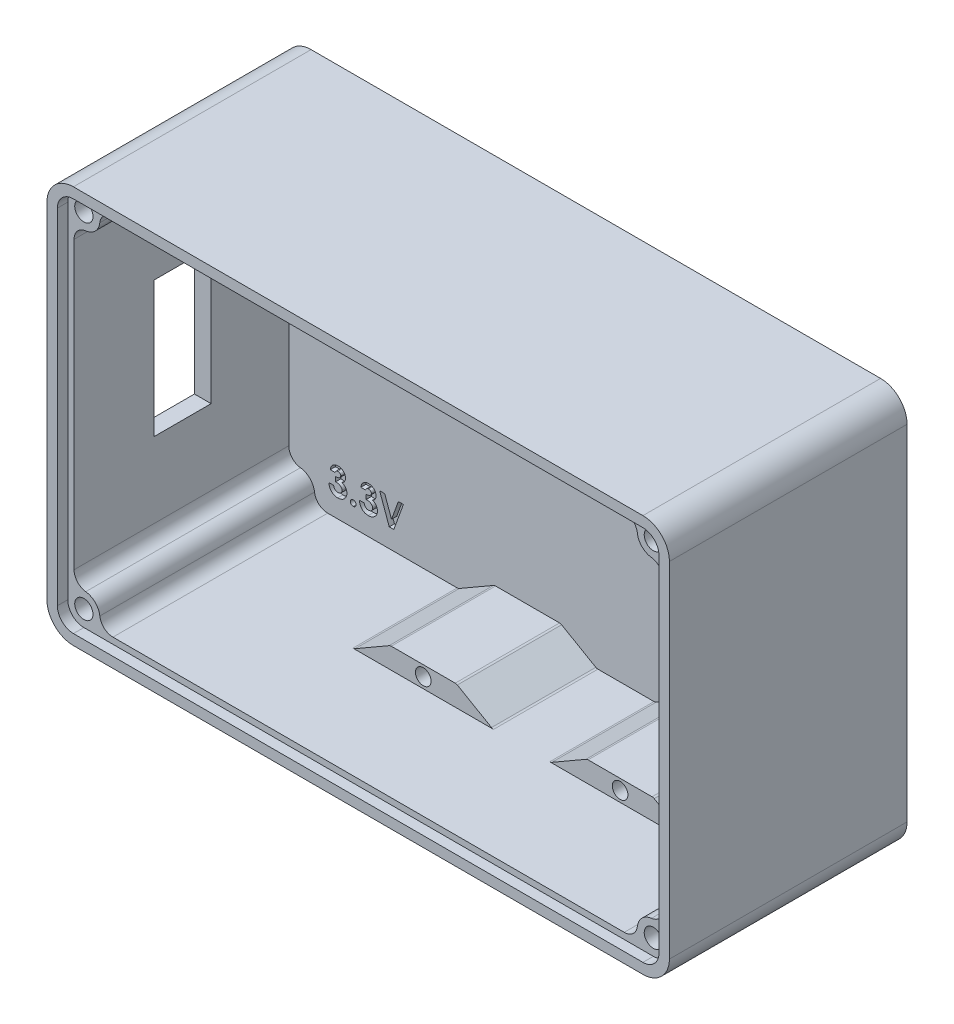
SolidWorks part; units mm, degrees
material "ABS"
ref_plane "Front Plane" through (0, 0, 0) normal (0, 0, 1) x (1, 0, 0)
ref_plane "Top Plane" through (0, 0, 0) normal (0, 1, 0) x (1, 0, 0)
ref_plane "Right Plane" through (0, 0, 0) normal (1, 0, 0) x (0, 0, -1)
sketch "OdroidOutline" plane through (0, 0, 0) normal (0, 0, 1) x (1, 0, 0)
  line L1 (42.5, -28) -> (-42.5, -28)
  line L2 (42.5, -28) -> (42.5, 28)
  line L3 (42.5, 28) -> (-42.5, 28)
  line L4 (-42.5, -28) -> (-42.5, 28)
  line L5 (42.5, -28) -> (-42.5, 28) construction
  line L6 (42.5, 28) -> (-42.5, -28) construction
  line L7 (-19, 24.5) -> (39, 24.5) construction
  line L8 (-19, 24.5) -> (-19, -24.5) construction
  line L9 (-19, -24.5) -> (39, -24.5) construction
  line L10 (39, 24.5) -> (39, -24.5) construction
  line L11 (-44, 25.54) -> (-22.3, 25.54)
  line L12 (-44, 25.54) -> (-44, 9.96)
  line L13 (-44, 9.96) -> (-22.3, 9.96)
  line L14 (-22.3, 25.54) -> (-22.3, 9.96)
  line L15 (-44, 5.565) -> (-26.44, 5.565)
  line L16 (-44, 5.565) -> (-44, -7.565)
  line L17 (-44, -7.565) -> (-26.44, -7.565)
  line L18 (-26.44, 5.565) -> (-26.44, -7.565)
  line L19 (-44, -12.435) -> (-26.44, -12.435)
  line L20 (-44, -12.435) -> (-44, -25.565)
  line L21 (-44, -25.565) -> (-26.44, -25.565)
  line L22 (-26.44, -12.435) -> (-26.44, -25.565)
  circle A0 centre (-19, 24.5) radius 1.25
  circle A1 centre (39, 24.5) radius 1.25
  circle A2 centre (39, -24.5) radius 1.25
  circle A3 centre (-19, -24.5) radius 1.25
  point P0 (0, 0)
  point P26 (-44, 17.75)
  point P27 (-44, -1)
  point P28 (-44, -19)
  dimension "D7" = 2.5
  dimension "D1" = 85
  dimension "D2" = 56
  dimension "D3" = 58
  dimension "D4" = 49
  dimension "D5" = 3.5
  dimension "D6" = 3.5
  dimension "D8" = 10.25
  dimension "D9" = 29
  dimension "D10" = 47
  dimension "D11" = 15.58
  dimension "D12" = 21.7
  dimension "D13" = 13.13
  dimension "D14" = 17.56
  dimension "D15" = 1.5
sketch "BatteryOutline" plane through (0, 0, 0) normal (0, 0, 1) x (1, 0, 0)
  line L0 (-3.8213, -21.195) -> (-3.8213, 21.195) construction
  line L2 (42.5, 0) -> (-3.8213, 0) construction
  line L3 (42.5, -28) -> (42.5, 28) construction
  line L4 (-3.8213, 21.195) -> (-3.8213, 24.5) construction
  line L7 (33.9287, -30.5) -> (-41.5713, -30.5)
  line L8 (33.9287, -30.5) -> (33.9287, 30.5)
  line L9 (33.9287, 30.5) -> (-41.5713, 30.5)
  line L10 (-41.5713, -30.5) -> (-41.5713, 30.5)
  line L11 (33.9287, -30.5) -> (-41.5713, 30.5) construction
  line L12 (33.9287, 30.5) -> (-41.5713, -30.5) construction
  circle A0 centre (-3.8213, 21.195) radius 1.75
  circle A1 centre (-3.8213, -21.195) radius 1.75
  point P3 (-3.8213, 0)
  dimension "D2" = 3.5
  dimension "D1" = 42.39
  dimension "D3" = 75.5
  dimension "D4" = 61
sketch "Sketch4" plane through (0, 0, 0) normal (0, 0, 1) x (1, 0, 0)
  line L0 (53.5, 0) -> (-53.5, 0) construction
  line L1 (53.5, -15) -> (53.5, 15) construction
  line L2 (-53.5, -15) -> (-53.5, 15) construction
  circle A0 centre (53.5, 15) radius 1.75
  circle A1 centre (-53.5, 15) radius 1.75
  circle A2 centre (-53.5, -15) radius 1.75
  circle A3 centre (53.5, -15) radius 1.75
  point P5 (0, 0)
  point P6 (53.5, 0)
  point P9 (-53.5, 0)
  dimension "D1" = 3.5
  dimension "D2" = 30
  dimension "D3" = 107
sketch "Sketch5" plane through (0, 0, 0) normal (0, 0, 1) x (1, 0, 0)
  line L0 (42.61, 34.9) -> (-66.61, 34.9)
  line L1 (42.61, -38.1) -> (-66.61, -38.1)
  line L2 (47.69, -33.02) -> (47.69, 33.02)
  line L3 (42.61, 38.1) -> (-66.61, 38.1)
  line L4 (-71.69, -33.02) -> (-71.69, 33.02)
  line L5 (47.69, -38.1) -> (-71.69, 38.1) construction
  line L6 (47.69, 38.1) -> (-71.69, -38.1) construction
  line L7 (-68.49, -33.02) -> (-68.49, 33.02)
  line L8 (42.61, -34.9) -> (-66.61, -34.9)
  line L9 (44.49, -33.02) -> (44.49, 33.02)
  line L10 (47.575, 0) -> (-47.575, 0) construction
  line L11 (0, 0) -> (0, 14.5835) construction
  arc A0 (-66.61, -38.1) -> (-71.69, -33.02) centre (-66.61, -33.02) cw
  arc A1 (42.61, -38.1) -> (47.69, -33.02) centre (42.61, -33.02) ccw
  arc A2 (47.69, 33.02) -> (42.61, 38.1) centre (42.61, 33.02) ccw
  arc A3 (-66.61, 38.1) -> (-71.69, 33.02) centre (-66.61, 33.02) ccw
  arc A4 (-66.61, 34.9) -> (-68.49, 33.02) centre (-66.61, 33.02) ccw
  arc A5 (-66.61, -34.9) -> (-68.49, -33.02) centre (-66.61, -33.02) cw
  arc A6 (42.61, -34.9) -> (44.49, -33.02) centre (42.61, -33.02) ccw
  arc A7 (44.49, 33.02) -> (42.61, 34.9) centre (42.61, 33.02) ccw
  point P16 (-12, 0)
  dimension "D6" = 5.08
  dimension "D2" = 119.38
  dimension "D4" = 12
  dimension "D3" = 3.2
extrude "Enclosure Base" add sketch "Sketch5" along normal blind 2.4 contours L3 A3 L4 A0 L1 A1 L2 A2
extrude "Enclosure Wall" add sketch "Sketch5<3>" along normal blind 43.18 from surface contours L3 A3 L4 A0 L1 A1 L2 A2 A7 L9 A6 L8 A5 L7 A4 L0 region at (-12, -36.6837, 0) starting at face at (-12, 0, 2.4)
sketch "Sketch5<3>" plane through (0, 0, 0) normal (0, 0, 1) x (1, 0, 0) same geometry as "Sketch5"
sketch "Sketch6" plane through (0, 0, 2.4) normal (0, 0, 1) x (1, 0, 0)
  line L0 (42.5, 28) -> (-42.5, 28) construction
  circle A0 centre (-19, 24.5) radius 3.5
  circle A1 centre (-19, -24.5) radius 3.5
  circle A2 centre (39, 24.5) radius 3.5
  circle A3 centre (39, -24.5) radius 3.5
  circle A4 centre (39, -24.5) radius 1.25 construction
  circle A5 centre (39, 24.5) radius 1.25 construction
  circle A6 centre (-19, -24.5) radius 1.25 construction
  circle A7 centre (-19, 24.5) radius 1.25 construction
  circle A8 centre (39, -24.5) radius 1.25
  circle A9 centre (39, 24.5) radius 1.25
  circle A10 centre (-19, -24.5) radius 1.25
  circle A11 centre (-19, 24.5) radius 1.25
extrude "Odroid Mount Spacer" [suppressed] add sketch "Sketch6" along normal blind 15
sketch "Sketch7" plane through (-71.69, 0, 0) normal (-1, 0, 0) x (0, 0, 1)
  line L0 (47.575, 0) -> (-47.575, 0) construction
  line L1 (28.29, -13) -> (17.29, -13)
  line L2 (28.29, -13) -> (28.29, 13)
  line L3 (28.29, 13) -> (17.29, 13)
  line L4 (17.29, -13) -> (17.29, 13)
  line L5 (28.29, -13) -> (17.29, 13) construction
  line L6 (28.29, 13) -> (17.29, -13) construction
  line L7 (22.79, 33.02) -> (22.79, 0) construction
  line L8 (45.58, 33.02) -> (0, 33.02) construction
  point P0 (22.79, 0)
  dimension "D1" = 26
  dimension "D2" = 11
extrude "Power Switch Hole" cut sketch "Sketch7" against normal blind 7.112
sketch "Sketch8" plane through (0, 0, 2.4) normal (0, 0, 1) x (1, 0, 0)
  line L0 (-60.9934, 25.8776) -> (-60.9934, -31.2724) construction
  line L4 (47.69, 38.1) -> (-71.69, -38.1) construction
  text T0 "<b>3.3V</b>" font "Century Gothic" height 5.08
  text T1 "<b>5.0V</b>" font "Century Gothic" height 5.08
  text T2 "<b>Vin</b>" font "Century Gothic" height 3.175
  dimension "D1" = 57.15
extrude "Labeling" cut sketch "Sketch8" against normal blind 1
sketch "Sketch9" plane through (0, 0, 45.58) normal (0, 0, 1) x (1, 0, 0)
  line L0 (42.61, 34.9) -> (-66.61, 34.9) construction
  line L1 (44.49, -33.02) -> (44.49, 33.02) construction
  line L2 (42.61, -34.9) -> (-66.61, -34.9) construction
  line L3 (-68.49, -33.02) -> (-68.49, 33.02) construction
  line L4 (44.49, -33.02) -> (44.49, 33.02)
  line L5 (42.61, -34.9) -> (-66.61, -34.9)
  line L6 (-68.49, -33.02) -> (-68.49, 33.02)
  line L7 (42.61, 34.9) -> (-66.61, 34.9)
  line L8 (42.61, 36.1) -> (-66.61, 36.1)
  line L9 (-69.69, 33.02) -> (-69.69, -33.02)
  line L10 (-66.61, -36.1) -> (42.61, -36.1)
  line L11 (45.69, -33.02) -> (45.69, 33.02)
  line L12 (42.61, 36.1) -> (-66.61, 36.1)
  line L13 (-69.69, 33.02) -> (-69.69, -33.02)
  line L14 (-66.61, -36.1) -> (42.61, -36.1)
  line L15 (45.69, -33.02) -> (45.69, 33.02)
  arc A0 (44.49, 33.02) -> (42.61, 34.9) centre (42.61, 33.02) ccw construction
  arc A1 (42.61, -34.9) -> (44.49, -33.02) centre (42.61, -33.02) ccw construction
  arc A2 (-68.49, -33.02) -> (-66.61, -34.9) centre (-66.61, -33.02) ccw construction
  arc A3 (-66.61, 34.9) -> (-68.49, 33.02) centre (-66.61, 33.02) ccw construction
  arc A4 (44.49, 33.02) -> (42.61, 34.9) centre (42.61, 33.02) ccw
  arc A5 (42.61, -34.9) -> (44.49, -33.02) centre (42.61, -33.02) ccw
  arc A6 (-68.49, -33.02) -> (-66.61, -34.9) centre (-66.61, -33.02) ccw
  arc A7 (-66.61, 34.9) -> (-68.49, 33.02) centre (-66.61, 33.02) ccw
  arc A8 (45.69, 33.02) -> (42.61, 36.1) centre (42.61, 33.02) ccw
  arc A9 (-66.61, 36.1) -> (-69.69, 33.02) centre (-66.61, 33.02) ccw
  arc A10 (-69.69, -33.02) -> (-66.61, -36.1) centre (-66.61, -33.02) ccw
  arc A11 (42.61, -36.1) -> (45.69, -33.02) centre (42.61, -33.02) ccw
  arc A12 (45.69, 33.02) -> (42.61, 36.1) centre (42.61, 33.02) ccw
  arc A13 (-66.61, 36.1) -> (-69.69, 33.02) centre (-66.61, 33.02) ccw
  arc A14 (-69.69, -33.02) -> (-66.61, -36.1) centre (-66.61, -33.02) ccw
  arc A15 (42.61, -36.1) -> (45.69, -33.02) centre (42.61, -33.02) ccw
extrude "Top Cover Groove" cut sketch "Sketch9" against normal blind 2
sketch "Sketch10" plane through (0, 0, 0) normal (0, 0, 1) x (1, 0, 0)
  circle A0 centre (-66.61, 33.02) radius 3.08
  circle A1 centre (-66.61, -33.02) radius 3.08
  circle A2 centre (42.61, 33.02) radius 3.08
  circle A3 centre (42.61, -33.02) radius 3.08
  arc A4 (45.69, 33.02) -> (42.61, 36.1) centre (42.61, 33.02) ccw construction
  arc A5 (-66.61, 36.1) -> (-69.69, 33.02) centre (-66.61, 33.02) ccw construction
  arc A6 (-69.69, -33.02) -> (-66.61, -36.1) centre (-66.61, -33.02) ccw construction
  arc A7 (42.61, -36.1) -> (45.69, -33.02) centre (42.61, -33.02) ccw construction
  circle A8 centre (-66.61, 33.02) radius 1.75
  circle A9 centre (-66.61, -33.02) radius 1.75
  circle A10 centre (42.61, -33.02) radius 1.75
  circle A11 centre (42.61, 33.02) radius 1.75
  dimension "D1" = 3.5
extrude "Boss-Extrude4" add sketch "Sketch10" along normal up to surface (43.58 mm away) up to face at (-12, 0, 43.58)
fillet "Fillet1" radius 2.54 8 edges at (44.49, 30.5803, 22.99) (40.1703, 34.9, 22.99) (-64.1703, 34.9, 22.99) (-68.49, 30.5803, 22.99) (-68.49, -30.5803, 22.99) (-64.1703, -34.9, 22.99) (40.1703, -34.9, 22.99) (44.49, -30.5803, 22.99)
sketch "Sketch11" plane through (0, 0, 2.4) normal (0, 0, 1) x (1, 0, 0)
  line L1 (-29.649, 7.2199) -> (-52.199, 7.2199)
  line L2 (-29.649, 7.2199) -> (-29.649, 24.5199)
  line L3 (-29.649, 24.5199) -> (-52.199, 24.5199)
  line L4 (-52.199, 7.2199) -> (-52.199, 24.5199)
  line L5 (-29.649, 7.2199) -> (-52.199, 24.5199) construction
  line L6 (-29.649, 24.5199) -> (-52.199, 7.2199) construction
  point P0 (-40.924, 15.8699)
  dimension "D1" = 17.3
  dimension "D2" = 22.55
sketch "Sketch12" plane through (0, 0, 2.4) normal (0, 0, 1) x (1, 0, 0)
  line L0 (-22.6963, 30.5) -> (-22.6963, 30.9) construction
  line L1 (-9.4181, 34.9) -> (-35.9745, 34.9)
  line L2 (-9.4181, 34.9) -> (-16.3463, 30.9)
  line L3 (42.61, 34.9) -> (-66.61, 34.9) construction
  line L4 (-3.8213, 30.5) -> (-3.8213, 34.9) construction
  line L5 (-61.0289, 34.9) -> (37.0289, 34.9) construction
  line L6 (8.7037, 30.9) -> (21.4037, 30.9)
  line L7 (28.3319, 34.9) -> (21.4037, 30.9)
  line L8 (1.7755, 34.9) -> (28.3319, 34.9)
  line L9 (1.7755, 34.9) -> (8.7037, 30.9)
  line L10 (-41.5713, 30.5) -> (-3.8213, 30.5) construction
  line L11 (-41.5713, -30.5) -> (-41.5713, 30.5) construction
  line L12 (-16.3463, 30.9) -> (-29.0463, 30.9)
  line L13 (-35.9745, 34.9) -> (-29.0463, 30.9)
  line L14 (-9.4181, 34.9) -> (-29.0463, 30.9) construction
  line L15 (-16.3463, 30.9) -> (-35.9745, 34.9) construction
  line L16 (33.9287, 30.5) -> (-41.5713, 30.5) construction
  line L17 (37.0289, 34.9) -> (-61.0289, 34.9) construction
  line L18 (-3.8213, -30.5) -> (-3.8213, -34.9) construction
  line L19 (33.9287, -30.5) -> (-41.5713, -30.5) construction
  line L20 (-61.0289, -34.9) -> (37.0289, -34.9) construction
  line L21 (-41.5713, -30.5) -> (-3.8213, -30.5) construction
  line L22 (-35.1963, -30.9) -> (-10.1963, -30.9) construction
  line L23 (-10.1963, -30.9) -> (-10.1963, -32.9) construction
  line L24 (-10.1963, -32.9) -> (-18.6963, -32.9) construction
  line L25 (-18.6963, -32.9) -> (-18.6963, -34.9) construction
  line L26 (-18.6963, -34.9) -> (-26.6963, -34.9) construction
  line L27 (-26.6963, -34.9) -> (-26.6963, -32.9) construction
  line L28 (-26.6963, -32.9) -> (-35.1963, -32.9) construction
  line L29 (-35.1963, -32.9) -> (-35.1963, -30.9) construction
  line L30 (-22.6963, -30.5) -> (-22.6963, -34.9) construction
  line L31 (19.0537, -32.9) -> (27.5537, -32.9) construction
  line L32 (19.0537, -34.9) -> (19.0537, -32.9) construction
  line L33 (11.0537, -34.9) -> (19.0537, -34.9) construction
  line L34 (11.0537, -32.9) -> (11.0537, -34.9) construction
  line L35 (2.5537, -32.9) -> (11.0537, -32.9) construction
  line L36 (2.5537, -30.9) -> (2.5537, -32.9) construction
  line L37 (27.5537, -30.9) -> (2.5537, -30.9) construction
  line L38 (27.5537, -32.9) -> (27.5537, -30.9) construction
  line L43 (33.9287, -30.5) -> (33.9287, 30.5) construction
  line L44 (34.3287, 25.25) -> (40.3287, 19.25)
  line L45 (34.3287, 25.25) -> (34.3287, 5.25)
  line L46 (34.3287, 5.25) -> (40.3287, 11.25)
  line L47 (40.3287, 19.25) -> (40.3287, 11.25) construction
  line L48 (33.9287, 0) -> (44.49, 0) construction
  line L49 (44.49, 27.4389) -> (44.49, -27.4389) construction
  line L50 (33.9287, 0) -> (33.9287, 30.5) construction
  line L51 (33.9287, 15.25) -> (34.3287, 15.25) construction
  line L56 (-22.6963, 30.9) -> (-22.6963, 34.8972) construction
  line L57 (25.069, 0) -> (-25.069, 0) construction
  line L58 (40.3287, 19.25) -> (44.49, 19.25)
  line L59 (44.49, -27.4389) -> (44.49, 27.4389) construction
  line L60 (44.49, 19.25) -> (44.49, 11.25)
  line L61 (44.49, 11.25) -> (40.3287, 11.25)
  line L62 (44.49, -19.25) -> (44.49, -11.25)
  line L63 (40.3287, -19.25) -> (44.49, -19.25)
  line L64 (34.3287, -25.25) -> (40.3287, -19.25)
  line L65 (34.3287, -25.25) -> (34.3287, -5.25)
  line L66 (34.3287, -5.25) -> (40.3287, -11.25)
  line L67 (44.49, -11.25) -> (40.3287, -11.25)
  circle A0 centre (-22.6963, 32.8986) radius 1.5
  circle A1 centre (15.0537, 32.8986) radius 1.5
  circle A2 centre (-22.6963, -32.8986) radius 1.5
  circle A3 centre (15.0537, -32.8986) radius 1.5
  point P0 (-22.6963, 32.1941)
  point P22 (-8.875, 30.5)
  point P24 (-22.6963, 30.5)
  point P30 (-22.6963, -30.5)
  point P46 (-22.6963, -30.9)
  point P68 (33.9287, 15.25)
  dimension "D13" = 3
  dimension "D1" = 0.4
  dimension "D2" = 30
  dimension "D3" = 30
  dimension "D4" = 2
  dimension "D5" = 0.4
  dimension "D6" = 8
  dimension "D7" = 25
  dimension "D8" = 45
  dimension "D9" = 45
  dimension "D10" = 0.4
  dimension "D11" = 6
  dimension "D12" = 20
  dimension "D14" = 12.7
extrude "Boss-Extrude5" add sketch "Sketch12" along normal blind 20 contours L13 L1 L2 L12 A0 | L9 L8 L7 L6 A1 region at (-13.0165, 33.1326, 2.4) region at (5.3739, 33.1326, 2.4)
extrude "Boss-Extrude6" add sketch "Sketch12<3>" along normal blind 20.066 contours L47 L44 L45 L46 | L64 L62 region at (38.4638, 15.25, 2.4) region at (38.4638, -15.25, 2.4)
sketch "Sketch12<3>" plane through (0, 0, 2.4) normal (0, 0, 1) x (1, 0, 0) same geometry as "Sketch12"
mirror "Mirror1" about plane through (0, 0, 0) normal (0, 1, 0) of "Boss-Extrude5"
fillet "Fillet4" radius 0.8 28 edges at (-9.4181, -34.9, 12.4) (-9.4181, 34.9, 12.4) (-16.3463, 30.9, 12.4) (-35.9745, 34.9, 12.4) (28.3319, 34.9, 12.4) (21.4037, 30.9, 12.4) (1.7755, 34.9, 12.4) (1.7755, -34.9, 12.4) (8.7037, -30.9, 12.4) (21.4037, -30.9, 12.4) (28.3319, -34.9, 12.4) (-35.9745, -34.9, 12.4) (-29.0463, -30.9, 12.4) (-16.3463, -30.9, 12.4) (-29.0463, 30.9, 12.4) (8.7037, 30.9, 12.4) (44.49, 19.25, 12.433) (40.3287, 19.25, 12.433) (34.3287, 25.25, 12.433) (34.3287, 5.25, 12.433) (40.3287, 11.25, 12.433) (44.49, 11.25, 12.433) (44.49, -11.25, 12.433) (40.3287, -11.25, 12.433) (34.3287, -5.25, 12.433) (34.3287, -25.25, 12.433) (40.3287, -19.25, 12.433) (44.49, -19.25, 12.433)
ref_plane "Plane2" through (0, 0, 42.4) normal (0, 0, 1) x (1, 0, 0)
equation "\"D1@OdroidOutline\"=85mm"
equation "\"D2@OdroidOutline\"=56mm"
equation "\"D3@OdroidOutline\"=58mm"
equation "\"D4@OdroidOutline\"=49mm"
equation "\"D5@OdroidOutline\"=3.5mm"
equation "\"D6@OdroidOutline\"=3.5mm"
equation "\"D7@OdroidOutline\"=2.5mm"
equation "\"D9@OdroidOutline\"=29mm"
equation "\"D10@OdroidOutline\"=47mm"
equation "\"D11@OdroidOutline\"=15.58mm"
equation "\"D13@OdroidOutline\"=13.13mm"
equation "\"D15@OdroidOutline\"=1.5mm"
equation "\"D1@BatteryOutline\" = 42.39mm"
equation "\"D2@BatteryOutline\" = 3.5mm"
equation "\"D1@Sketch4\"=3.5mm"
equation "\"D2@Sketch4\"=30mm"
equation "\"D3@Sketch4\"=107mm"
equation "\"D3@Sketch5\"=3.2mm"
equation "\"D1@Enclosure Base\" = 2.4mm"
equation "\"D1@Enclosure Wall\"=1.7in"
equation "\"D1@Odroid Mount Spacer\"=15mm"
equation "\"D4@BatteryOutline\" = 61mm"
equation "\"D1@Sketch7\"=26mm"
equation "\"D2@Sketch7\"=11mm"
equation "\"D1@Labeling\" = 1mm"
equation "\"D1@Sketch9\"=2mm"
equation "\"D1@Top Cover Groove\" = 2mm"
equation "\"D1@Sketch10\"=3.50mm"
equation "\"D1@Sketch11\"=17.3mm"
equation "\"D2@Sketch11\"=22.55mm"
equation "\"D1@Sketch12\"=0.4mm"
equation "\"D1@Boss-Extrude5\"=20mm"
equation "\"D1@Fillet2\"=0.5mm"
equation "\"D5@Sketch12\"=0.4mm"
equation "\"D4@Sketch12\"=2mm"
equation "\"D6@Sketch12\"=8mm"
equation "\"D7@Sketch12\"=25mm"
equation "\"D1@Fillet3\"=1mm"
equation "\"D8@Sketch12\"=45"
equation "\"D9@Sketch12\"=45"
equation "\"D10@Sketch12\"=0.4mm"
equation "\"D11@Sketch12\"=6mm"
equation "\"D12@Sketch12\"=20mm"
equation "\"D13@Sketch12\"=3mm"
equation "\"D1@Fillet4\"=0.8mm"
equation "\"D4@Sketch5\"=12mm"
equation "\"D14@Sketch12\"=0.5"
